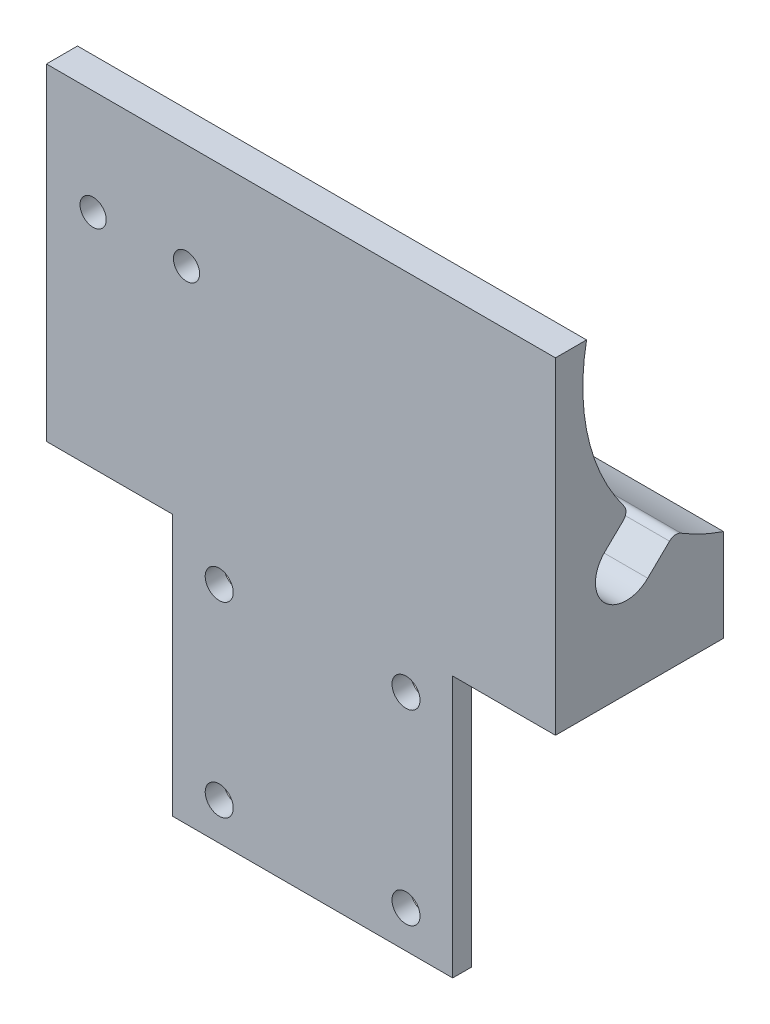
SolidWorks part; units mm, degrees
note: The reader was unsure of these and kept them because the rebuilt part matched: shared geometry of "Sketch1<4>", "Sketch3<4>", "Sketch8<3>", "Sketch8<4>", "Sketch1<8>".
ref_plane "Front Plane" through (0, 0, 0) normal (0, 0, 1) x (1, 0, 0)
ref_plane "Top Plane" through (0, 0, 0) normal (0, 1, 0) x (1, 0, 0)
ref_plane "Right Plane" through (0, 0, 0) normal (1, 0, 0) x (0, 0, -1)
sketch "Sketch1" plane through (0, 0, 0) normal (0, 0, 1) x (1, 0, 0)
  line L0 (-15, -46.5) -> (15, -46.5) construction
  line L1 (-16, 14) -> (16, 14)
  line L2 (-16, 14) -> (-16, -13.5)
  line L3 (-16, -13.5) -> (16, -13.5)
  line L4 (16, 14) -> (16, -13.5)
  line L5 (-16, -13.5) -> (16, -13.5)
  line L6 (-16, -13.5) -> (-16, -46.5)
  line L7 (-16, -46.5) -> (16, -46.5)
  line L8 (16, -13.5) -> (16, -46.5)
  line L10 (-16, -46.5) -> (-14.9693, -46.5)
  line L11 (-16, -46.5) -> (-16, -13.5)
  line L12 (-16, -13.5) -> (-14.9693, -13.5)
  line L13 (-14.9693, -46.5) -> (-14.9693, -13.5)
  line L14 (15, -46.5) -> (15, -28.5) construction
  line L15 (16, -46.5) -> (15, -46.5)
  line L16 (16, -46.5) -> (16, -13.5)
  line L17 (16, -13.5) -> (15, -13.5)
  line L18 (15, -46.5) -> (15, -13.5)
  line L19 (16, -13.5) -> (-16, -13.5) construction
  line L20 (16, -13) -> (16, -6.5) construction
  line L21 (-16, 13.5) -> (16, 13.5) construction
  line L22 (-16, 14) -> (16, 14) construction
  line L23 (-16, 14) -> (-16, 49)
  line L24 (-16, 49) -> (16, 49)
  line L25 (16, 14) -> (16, 49)
  line L26 (9.5, 20.5152) -> (0, 15.0303)
  line L27 (0, 15.0303) -> (-9.5, 20.5152)
  line L28 (-9.5, 20.5152) -> (-9.5, 31.4848)
  line L29 (-9.5, 31.4848) -> (0, 36.9697)
  line L30 (0, 36.9697) -> (9.5, 31.4848)
  line L31 (9.5, 31.4848) -> (9.5, 20.5152)
  line L32 (9.5, 31.4848) -> (-9.5, 20.5152) construction
  line L33 (-9.5, 31.4848) -> (9.5, 20.5152) construction
  line L34 (0, 15.0303) -> (0, 36.9697) construction
  line L35 (15.9091, -40.467) -> (12.5423, -46.5671)
  line L36 (12.5423, -46.5671) -> (5.5747, -46.5671)
  line L37 (5.5747, -46.5671) -> (2.0909, -40.533)
  line L38 (2.0909, -40.533) -> (5.4577, -34.4329)
  line L39 (5.4577, -34.4329) -> (12.4253, -34.4329)
  line L40 (12.4253, -34.4329) -> (15.9091, -40.467)
  line L41 (12.4253, -34.4329) -> (5.5747, -46.5671) construction
  line L42 (2.0909, -40.533) -> (15.9091, -40.467) construction
  line L43 (12.5423, -46.5671) -> (5.4577, -34.4329) construction
  line L44 (-2.0718, -40.5) -> (-5.5359, -46.5)
  line L45 (-5.5359, -46.5) -> (-12.4641, -46.5)
  line L46 (-12.4641, -46.5) -> (-15.9282, -40.5)
  line L47 (-15.9282, -40.5) -> (-12.4641, -34.5)
  line L48 (-12.4641, -34.5) -> (-5.5359, -34.5)
  line L49 (-5.5359, -34.5) -> (-2.0718, -40.5)
  line L50 (-5.5359, -34.5) -> (-12.4641, -46.5) construction
  line L51 (-15.9282, -40.5) -> (-2.0718, -40.5) construction
  line L52 (-5.5359, -46.5) -> (-12.4641, -34.5) construction
  circle A0 centre (8.5, -31.5) radius 1.5
  circle A1 centre (-8.5, -31.5) radius 1.5
  circle A2 centre (0, -43.5) radius 1.5
  circle A3 centre (-10, -10) radius 1.5
  circle A4 centre (10, -10) radius 1.5
  circle A5 centre (10, 10) radius 1.5
  circle A6 centre (-10, 10) radius 1.5
  circle A7 centre (0, 26) radius 6.1
  point P51 (0, 26)
  point P61 (9, -40.5)
  point P70 (-9, -40.5)
  dimension "D1" = 3
  dimension "D2" = 3
  dimension "D3" = 3
  dimension "D4" = 3
  dimension "D5" = 3
  dimension "D6" = 3
  dimension "D7" = 3
  dimension "D9" = 12.2
  dimension "D10" = 12.5
  dimension "D15" = 27.5
  dimension "D8" = 35
  dimension "D11" = 19
  dimension "D12" = 120
  dimension "D13" = 120
  dimension "D14" = 16
  dimension "D16" = 12
  dimension "D17" = 120
  dimension "D19" = 12
  dimension "D20" = 120
extrude "Boss-Extrude2" add sketch "Sketch1" along normal blind 4 contours L7 L18 L5 L13 A2 A1 A0 | L18 L7 L8 L3 | L4 L1 L2 L3 L5 A6 A5 A4 A3 | L1 L25 L24 L23 L30 L31 L26 L27 L28 L29 | L7 L13 L3 L6 | L31 L30 L29 L28 L27 L26 A7 | A7
extrude "Boss-Extrude3" add sketch "Sketch1<4>" against normal blind 20 contours L1 L25 L24 L23 L30 L31 L26 L27 L28 L29 | L31 L30 L29 L28 L27 L26 A7 | A7
sketch "Sketch1<4>" plane through (0, 0, 0) normal (0, 0, 1) x (1, 0, 0) same geometry as "Sketch1"
sketch "Sketch2" plane through (-16, 0, 0) normal (-1, 0, 0) x (0, 0, 1)
  circle A0 centre (-1.58, 25.9998) radius 1.5
  dimension "D3" = 3
extrude "Cut-Extrude3" cut sketch "Sketch2" against normal through all both and the other way through all
sketch "Sketch3" plane through (-16, 0, 0) normal (-1, 0, 0) x (0, 0, 1)
  line L0 (-1.2391, 30.2656) -> (0.717, 28.3692)
  line L1 (0.717, 28.3692) -> (-3.877, 23.6305)
  line L2 (-20, 14) -> (-20, 49) construction
  line L3 (4, 49) -> (-20, 49) construction
  line L4 (2.671, 49) -> (-20, 49)
  line L5 (-20, 49) -> (-20, 22.7781)
  line L6 (-6.2128, 25.895) -> (-3.877, 23.6305)
  arc A0 (-1.3431, 31.5835) -> (-1.2391, 30.2656) centre (-0.5431, 30.9835) ccw
  arc A1 (0.717, 28.3692) -> (-3.877, 23.6305) centre (-1.58, 25.9998) cw
  arc A2 (-6.2128, 25.895) -> (-7.4329, 26.0287) centre (-6.9089, 25.177) ccw
  arc A3 (-20, 22.7781) -> (-7.4329, 26.0287) centre (-18.9982, 44.8234) ccw
  arc A4 (-26.5932, 24.1035) -> (-7.4329, 26.0287) centre (-18.9982, 44.8234) ccw construction
  arc A5 (-1.3431, 31.5835) -> (2.671, 49) centre (-18.9982, 44.8234) ccw
  arc A6 (-1.3431, 31.5835) -> (3.0463, 43.8054) centre (-18.9982, 44.8234) ccw construction
  circle M1 centre (-1.58, 25.9998) radius 1.5
  line M2 (4, 49) -> (-20, 49)
  line M3 (-20, 49) -> (-20, 14)
extrude "Cut-Extrude4" cut sketch "Sketch3" against normal blind 5 contours A0 A5 A3 A2 L6 L1 L0 M2 M3 M1
extrude "Cut-Extrude5" cut sketch "Sketch3<4>" along normal blind 5 from surface at -32 contours A0 A5 A3 A2 L6 L1 L0 M2 M3 M1
sketch "Sketch3<4>" plane through (-16, 0, 0) normal (-1, 0, 0) x (0, 0, 1) same geometry as "Sketch3"
sketch "Sketch5" plane through (0, 0, 4) normal (0, 0, 1) x (1, 0, 0)
  line L0 (17.8253, -40.465) -> (-17.3183, -40.5014)
  line L1 (-17.3183, -40.5014) -> (-17.1295, -46.5)
  line L2 (-17.1295, -46.5) -> (17.9162, -46.5)
  line L3 (17.9162, -46.5) -> (17.8253, -40.465)
  line L4 (-9.5079, -40.4933) -> (-9.5079, -46.5)
  line L5 (-9.5079, -46.5) -> (10.3669, -46.5)
  line L6 (10.3669, -46.5) -> (10.3669, -40.4727)
  line M1 (15, -46.5) -> (16, -46.5)
  line M2 (16, -46.5) -> (16, 49)
  line M4 (-16, 49) -> (-16, -46.5)
  line M5 (-16, -46.5) -> (-14.9693, -46.5)
  line M6 (-14.9693, -46.5) -> (-14.9693, -42.1609)
  line M7 (-14.9693, -42.1609) -> (-15.9282, -40.5)
  line M17 (15.9091, -40.467) -> (15, -42.1142)
  line M18 (15, -42.1142) -> (15, -46.5)
extrude "Cut-Extrude6" cut sketch "Sketch5" against normal through all contours L0 M7 M4 M5 M6 | L6 L2 L0 M18 M17 | L0 M2 M17 M18 M1 | L2 L3 L0 M2
sketch "Sketch8" plane through (-16, 0, 0) normal (-1, 0, 0) x (0, 0, 1)
  line L0 (-1.2391, 30.2656) -> (0.717, 28.3692)
  line L1 (-3.877, 23.6305) -> (-6.2128, 25.895)
  line L2 (-20, 22.7781) -> (-20, 14)
  line L3 (-20, 14) -> (4, 14)
  line L4 (4, 49) -> (4, -40.5001) construction
  line L5 (4, 14) -> (4, 49)
  line L6 (4, 49) -> (2.671, 49)
  line L7 (2.671, 49) -> (-20, 49)
  line L8 (-20, 49) -> (-20, 22.7781)
  arc A0 (2.671, 49) -> (-1.3431, 31.5835) centre (-18.9982, 44.8234) cw
  arc A1 (-1.3431, 31.5835) -> (-1.2391, 30.2656) centre (-0.5431, 30.9835) ccw
  arc A2 (0.717, 28.3692) -> (-3.877, 23.6305) centre (-1.58, 25.9998) cw
  arc A3 (-6.2128, 25.895) -> (-7.4329, 26.0287) centre (-6.9089, 25.177) ccw
  arc A4 (-7.4329, 26.0287) -> (-20, 22.7781) centre (-18.9982, 44.8234) cw
  circle A5 centre (-1.58, 25.9998) radius 2.574
  arc A6 (-1.3431, 31.5835) -> (-7.4329, 26.0287) centre (-18.9982, 44.8234) cw
  line M3 (4, -40.5001) -> (4, 49)
  line M4 (4, 49) -> (2.671, 49)
  arc M5 (2.671, 49) -> (-1.3431, 31.5835) centre (-18.9982, 44.8234) cw
  arc M6 (-1.3431, 31.5835) -> (-1.2391, 30.2656) centre (-0.5431, 30.9835) ccw
  line M7 (-1.2391, 30.2656) -> (0.717, 28.3692)
  arc M8 (0.717, 28.3692) -> (-3.877, 23.6305) centre (-1.58, 25.9998) cw
  line M9 (-3.877, 23.6305) -> (-6.2128, 25.895)
  arc M10 (-6.2128, 25.895) -> (-7.4329, 26.0287) centre (-6.9089, 25.177) ccw
  arc M11 (-7.4329, 26.0287) -> (-20, 22.7781) centre (-18.9982, 44.8234) cw
  line M12 (-20, 22.7781) -> (-20, 14)
  line M13 (-20, 14) -> (0, 14)
extrude "Boss-Extrude5" add sketch "Sketch8" along normal blind 12.5 contours L3 M13 M3 M4 M5 M6 M7 M8 M9 M10 M11 M12
sketch "Sketch7" plane through (0, 0, 4) normal (0, 0, 1) x (1, 0, 0)
  line L1 (-28.5, 49) -> (-8.5, 49)
  line L2 (-28.5, 49) -> (-28.5, 26.5)
  line L3 (-28.5, 26.5) -> (-8.5, 26.5)
  line L4 (-8.5, 49) -> (-8.5, 26.5)
  line L6 (-28.5, 14) -> (-28.5, 49) construction
  line L7 (-28.5, 49) -> (16, 49) construction
  circle A0 centre (-23.5, 37.75) radius 1.4
  circle A1 centre (-13.5, 37.75) radius 1.4
  dimension "D3" = 2.8
  dimension "D4" = 2.8
  dimension "D6" = 11.25
  dimension "D7" = 15
  dimension "D9" = 0
  dimension "D1" = 22.5
  dimension "D2" = 11.25
  dimension "D5" = 5
  dimension "D8" = 0
  dimension "D10" = 5
extrude "Cut-Extrude7" cut sketch "Sketch7" against normal blind 20 contours A1 | A0
extrude "Boss-Extrude6" add sketch "Sketch8<3>" against normal blind 10 from surface at -32 contours L3 M13 M3 M4 M5 M6 M7 M8 M9 M10 M11 M12 starting at face at (16, 17.7031, -3.4221)
sketch "Sketch8<3>" plane through (-16, 0, 0) normal (-1, 0, 0) x (0, 0, 1) same geometry as "Sketch8"
extrude "Cut-Extrude8" cut sketch "Sketch8<4>" against normal through all contours A6 L7 L8 M5 M11
sketch "Sketch8<4>" plane through (-16, 0, 0) normal (-1, 0, 0) x (0, 0, 1) same geometry as "Sketch8"
sketch "Sketch9" plane through (0, 0, 4) normal (0, 0, 1) x (1, 0, 0)
  line L0 (-28.5, 49) -> (26, 49) construction
  line L1 (26, 49) -> (-28.5, 49)
  line L2 (26, 49) -> (26, 14)
  line L3 (26, 14) -> (-28.5, 14)
  line L4 (-28.5, 49) -> (-28.5, 14)
  line L5 (26, 49) -> (-28.5, 14) construction
  line L6 (26, 14) -> (-28.5, 49) construction
  line L7 (16, 14) -> (-16, 14)
  line L8 (16, 14) -> (16, -14)
  line L9 (16, -14) -> (-16, -14)
  line L10 (-16, 14) -> (-16, -14)
  line L11 (16, 14) -> (-16, -14) construction
  line L12 (16, -14) -> (-16, 14) construction
  circle A0 centre (10, 10) radius 1.5
  circle A1 centre (10, -10) radius 1.5
  circle A2 centre (-10, -10) radius 1.5
  circle A3 centre (-10, 10) radius 1.5
  point P4 (-1.25, 26.5)
  point P11 (0, -1)
  circle M2 centre (-23.5, 37.75) radius 1.4
  circle M3 centre (-13.5, 37.75) radius 1.4
  line M15 (16, -40.4669) -> (16, 14)
  line M16 (16, 14) -> (26, 14)
  line M17 (26, 14) -> (26, 49)
  line M18 (26, 49) -> (-28.5, 49)
  line M19 (-28.5, 49) -> (-28.5, 14)
  line M20 (-28.5, 14) -> (-16, 14)
  line M21 (-16, 14) -> (-16, -40.5001)
  circle M25 centre (-10, 10) radius 1.5
  circle M26 centre (10, 10) radius 1.5
  circle M27 centre (10, -10) radius 1.5
  circle M28 centre (-10, -10) radius 1.5
  dimension "D1" = 28
extrude "Boss-Extrude7" add sketch "Sketch9" along normal blind 2 contours L3 M16 M17 M18 M19 M20 M3 M2 | L9 L3 M15 M21 M25 M27 M28 M26
extrude "Cut-Extrude9" cut sketch "Sketch1<8>" along normal up to vertex (4 mm away) contours L4 L1 L2 L3 L5 A6 A5 A4 A3 | L48 L49 L44 L7 L37 L38 L39 L40 L18 L5 L13 L47 A2 A1 A0 | L46 L47 L13 L3 L6 L7 | L18 L40 L35 L7 L8 L3
sketch "Sketch1<8>" plane through (0, 0, 0) normal (0, 0, 1) x (1, 0, 0) same geometry as "Sketch1"
sketch "Sketch11" plane through (0, 0, 6) normal (0, 0, 1) x (1, 0, 0)
  line L0 (-16, 14) -> (-28.5, 14) construction
  line L1 (-16, -14) -> (-15, -14)
  line L2 (-16, -14) -> (-16, 14)
  line L3 (-16, 14) -> (-15, 14)
  line L4 (-15, -14) -> (-15, 14)
  line L5 (-16, -14) -> (-15, 14) construction
  line L6 (-16, 14) -> (-15, -14) construction
  line L7 (16, -14) -> (-16, -14) construction
  line L8 (16, 14) -> (15, 14)
  line L9 (16, 14) -> (16, -14)
  line L10 (16, -14) -> (15, -14)
  line L11 (15, 14) -> (15, -14)
  line L12 (16, 14) -> (15, -14) construction
  line L13 (16, -14) -> (15, 14) construction
  point P4 (-15.5, 0)
  point P12 (15.5, 0)
  line M11 (-16, 14) -> (-16, -14)
  line M12 (-16, -14) -> (16, -14)
  line M13 (16, -14) -> (16, 14)
  dimension "D1" = 1
  dimension "D2" = 1
extrude "Cut-Extrude13" cut sketch "Sketch11" against normal through all contours L4 L3 M12 M11 | L8 L11 M12 M13
sketch "Sketch10" plane through (-28.5, 0, 0) normal (-1, 0, 0) x (0, 0, 1)
  line L0 (-20, 22.7781) -> (-20, 14)
  line L1 (-20, 14) -> (-12, 14)
  line L2 (-20, 14) -> (6, 14) construction
  line L3 (-12, 14) -> (-12, 23.8944)
  arc A0 (-7.4329, 26.0287) -> (-20, 22.7781) centre (-18.9982, 44.8234) cw
  line M3 (-20, 14) -> (6, 14)
  arc M12 (-7.4329, 26.0287) -> (-20, 22.7781) centre (-18.9982, 44.8234) cw
  line M13 (-20, 22.7781) -> (-20, 14)
  dimension "D1" = 8
extrude "Cut-Extrude10" cut sketch "Sketch10" against normal through all contours L3 M3 M12 M13
